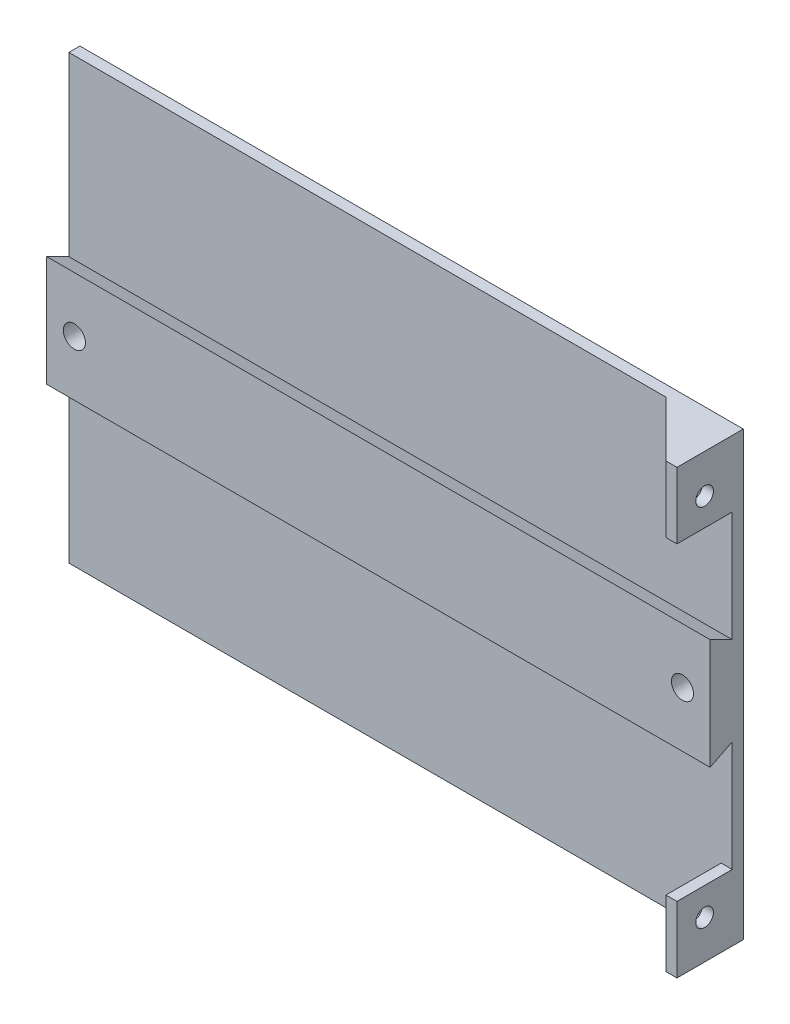
SolidWorks part; units mm, degrees
ref_plane "Front Plane" through (0, 0, 0) normal (1, 0, 0) x (0, 1, 0)
ref_plane "Top Plane" through (0, 0, 0) normal (0, 0, 1) x (0, 1, 0)
ref_plane "Right Plane" through (0, 0, 0) normal (0, 1, 0) x (-1, 0, 0)
sketch "Sketch1" plane through (0, 0, 0) normal (0, 0, 1) x (0, 1, 0)
  line L1 (-20, -30) -> (20, -30)
  line L2 (-20, -30) -> (-20, 30)
  line L3 (-20, 30) -> (20, 30)
  line L4 (20, -30) -> (20, 30)
  line L5 (-20, -30) -> (20, 30) construction
  line L6 (-20, 30) -> (20, -30) construction
  line L7 (-5, 30) -> (5, 30)
  line L8 (-5, 30) -> (-5, -30)
  line L9 (-5, -30) -> (5, -30)
  line L10 (5, 30) -> (5, -30)
  line L11 (-5, 30) -> (5, -30) construction
  line L12 (-5, -30) -> (5, 30) construction
  point P0 (0, 0)
  point P6 (0, 0)
  dimension "D1" = 40
  dimension "D2" = 60
  dimension "D3" = 10
extrude "Boss-Extrude1" add sketch "Sketch1" along normal blind 1 contours L8 L3 L2 L1 | L3 L10 L1 L4 region at (0, -12.5, 0) region at (0, 12.5, 0)
extrude "Boss-Extrude2" add sketch "Sketch1<3>" along normal blind 3 contours L10 L3 L8 L1 region at (0, 0, 0)
sketch "Sketch1<3>" plane through (0, 0, 0) normal (0, 0, 1) x (0, 1, 0) same geometry as "Sketch1"
sketch "Sketch2" plane through (30, 0, 0) normal (1, 0, 0) x (0, 1, 0)
  line L0 (-5, 1) -> (-4, 1)
  line L1 (5, 1) -> (4, 1)
  line L2 (-5, 3) -> (-4, 1)
  line L3 (4, 1) -> (5, 3)
  line L4 (-5, 1) -> (-5, 3)
  line L5 (5, 1) -> (5, 3)
extrude "Cut-Extrude1" cut sketch "Sketch2" against normal blind 66
sketch "Sketch5" plane through (0, 0, 3) normal (0, 0, 1) x (1, 0, 0)
  circle A0 centre (-27.5, 0) radius 1
  circle A1 centre (27.5, 0) radius 1
extrude "Cut-Extrude2" cut sketch "Sketch5" against normal blind 10
sketch "Sketch7" plane through (30, 0, 0) normal (1, 0, 0) x (0, 1, 0)
  line L1 (-20, 0) -> (-14, 0)
  line L2 (-20, 0) -> (-20, 6)
  line L3 (-20, 6) -> (-14, 6)
  line L4 (-14, 0) -> (-14, 6)
  line L5 (20, 0) -> (14, 0)
  line L6 (20, 0) -> (20, 6)
  line L7 (20, 6) -> (14, 6)
  line L8 (14, 0) -> (14, 6)
  dimension "D1" = 6
  dimension "D2" = 6
  dimension "D3" = 6
  dimension "D4" = 6
extrude "Boss-Extrude7" add sketch "Sketch7" against normal blind 1
sketch "Sketch10" plane through (0, -20, 0) normal (0, -1, 0) x (1, 0, 0)
  line L0 (29, 6) -> (24, 1)
  line L1 (-30, 1) -> (30, 1) construction
  line L2 (24, 1) -> (29, 1)
  line L3 (29, 1) -> (29, 6)
extrude "Boss-Extrude8" add sketch "Sketch10" against normal blind 1
sketch "Sketch11" plane through (0, 20, 0) normal (0, 1, 0) x (-1, 0, 0)
  line L0 (-29, 6) -> (-24, 1)
  line L1 (30, 1) -> (-30, 1) construction
  line L2 (-24, 1) -> (-29, 1)
  line L3 (-29, 1) -> (30, 1) construction
  line L4 (-29, 1) -> (-29, 6)
extrude "Boss-Extrude9" add sketch "Sketch11" against normal blind 1
sketch "Sketch12" plane through (29, 0, 0) normal (-1, 0, 0) x (0, -1, 0)
  line L0 (0, 0) -> (0, 3)
  line L1 (20, 0) -> (16.5, 0)
  line L2 (20, 0) -> (20, 3.5)
  line L3 (20, 3.5) -> (16.5, 3.5)
  line L4 (16.5, 0) -> (16.5, 3.5)
  line L5 (5, 3) -> (-5, 3) construction
  line L6 (-20, 3.5) -> (-16.5, 3.5)
  line L7 (-16.5, 0) -> (-16.5, 3.5)
  line L8 (-20, 0) -> (-16.5, 0)
  line L9 (-20, 0) -> (-20, 3.5)
  point P1 (16.5, 3.5)
  point P11 (-16.5, 3.5)
  dimension "D1" = 3.5
  dimension "D2" = 3.5
hole_wizard "M2 Tapped Hole1" positions "Sketch12" profile "Sketch14" tap size "M2" standard "DIN"
sketch "Sketch14" plane through (29, 16.5, 3.5) normal (0, 1, 0) x (0, 0, 1)
  line L0 (0, 0) -> (0, 6.4807)
  line L1 (0, 6.4807) -> (0.8, 6)
  line L2 (0.8, 6) -> (0.8, 0)
  line L5 (0.8, 0) -> (0, 0)
  line L10 (0, 6.4807) -> (-0.8, 6) construction
  line L11 (0, -6.35) -> (0, 107.95) construction
  dimension "Tap Drill Dia." = 1.6
  dimension "Tap Drill Depth" = 6
  dimension "Drill Angle" = 118
cosmetic thread "Hole Thread1" parameters "D1"=4, "D2"=2
cosmetic thread "Hole Thread2" parameters "D1"=4, "D2"=2
sketch "Sketch4" plane through (0, 0, 3) normal (0, 0, 1) x (1, 0, 0)
  line L0 (30, -5) -> (30, 5) construction
  line L1 (-30, -2.5) -> (30, -2.5)
  line L2 (-30, -2.5) -> (-30, 2.5)
  line L3 (-30, 2.5) -> (30, 2.5)
  line L4 (30, -2.5) -> (30, 2.5)
  line L5 (-30, -2.5) -> (30, 2.5) construction
  line L6 (-30, 2.5) -> (30, -2.5) construction
  point P0 (0, 0)
  dimension "D1" = 5
